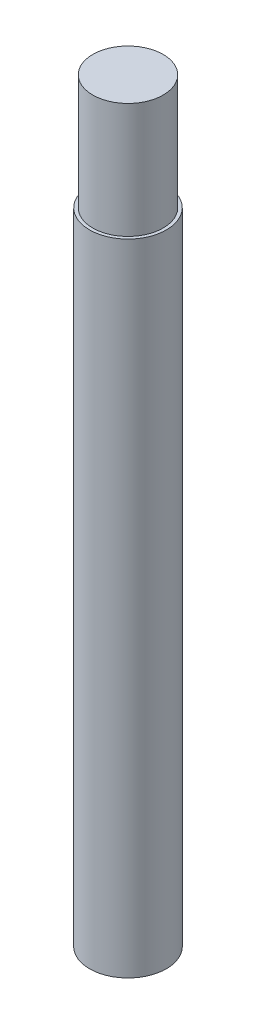
SolidWorks part; units mm, degrees
material "AISI 316 Stainless Steel"
ref_plane "Front Plane" through (0, 0, 0) normal (0, 0, 1) x (1, 0, 0)
ref_plane "Top Plane" through (0, 0, 0) normal (0, 1, 0) x (1, 0, 0)
ref_plane "Right Plane" through (0, 0, 0) normal (1, 0, 0) x (0, 0, -1)
ref_axis "Axis1" through (0, 0, -88.99) along (0, 0, 1)
ref_axis "Axis2" through (0, -55, 0) along (0, 1, 0)
ref_axis "Axis3" through (-88.99, 0, 0) along (1, 0, 0)
sketch "Sketch1" plane through (0, 0, 0) normal (0, 1, 0) x (1, 0, 0)
  circle A0 centre (0, 0) radius 3
  dimension "D1" = 6
extrude "Boss-Extrude1" add sketch "Sketch1" along normal blind 50
sketch "Sketch2" plane through (0, 50, 0) normal (0, 1, 0) x (1, 0, 0)
  circle A0 centre (0, 0) radius 2.75
  dimension "D1" = 5.5
extrude "Boss-Extrude2" add sketch "Sketch2" along normal blind 9
